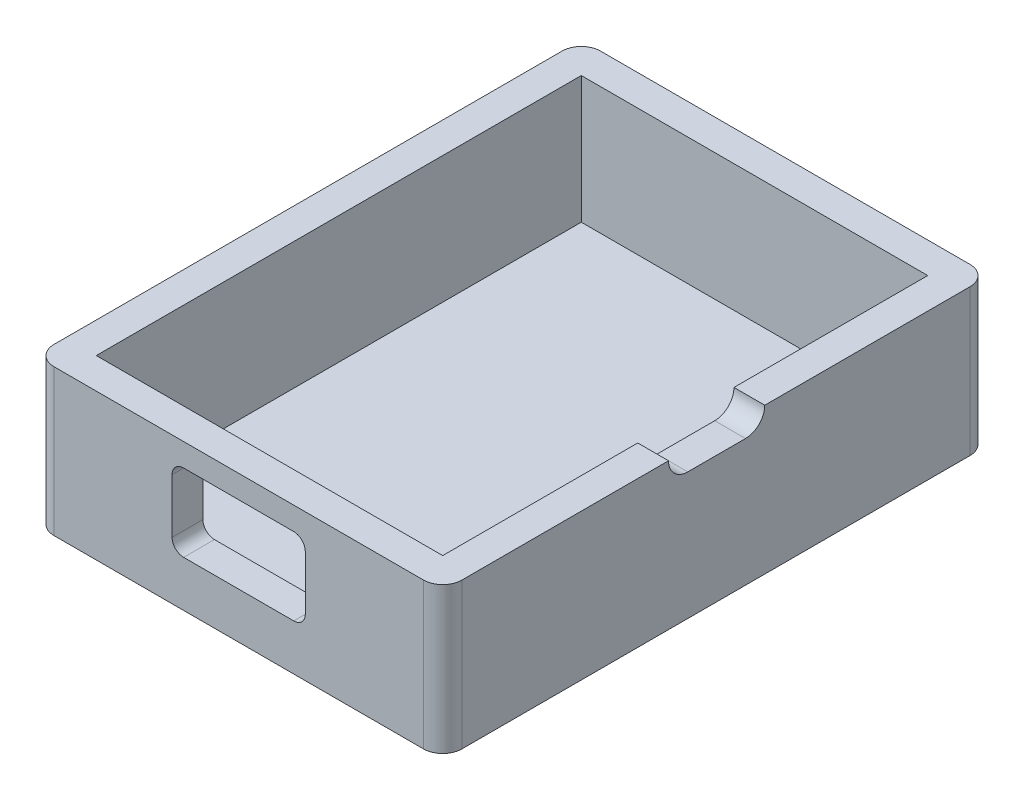
SolidWorks part; units mm, degrees
ref_plane "Front Plane" through (0, 0, 0) normal (0, 0, 1) x (1, 0, 0)
ref_plane "Top Plane" through (0, 0, 0) normal (0, 1, 0) x (1, 0, 0)
ref_plane "Right Plane" through (0, 0, 0) normal (1, 0, 0) x (0, 0, -1)
sketch "Sketch1" plane through (0, 0, 0) normal (0, 1, 0) x (1, 0, 0)
  line L1 (-53, -71) -> (53, -71)
  line L2 (-53, -71) -> (-53, 71)
  line L3 (-53, 71) -> (53, 71)
  line L4 (53, -71) -> (53, 71)
  line L5 (-53, -71) -> (53, 71) construction
  line L6 (-53, 71) -> (53, -71) construction
  point P0 (0, 0)
  dimension "D1" = 106
  dimension "D2" = 142
extrude "Boss-Extrude1" add sketch "Sketch1" along normal blind 5
sketch "Sketch2" plane through (0, 5, 0) normal (0, 1, 0) x (1, 0, 0)
  line L0 (53, -71) -> (53, 71) construction
  line L1 (-53, -71) -> (53, -71)
  line L2 (-53, -71) -> (-53, -63)
  line L3 (-53, -63) -> (53, -63)
  line L4 (53, -71) -> (53, -63)
  dimension "D1" = 8
extrude "Boss-Extrude2" add sketch "Sketch2" along normal blind 33
sketch "Sketch3" plane through (0, 5, 0) normal (0, 1, 0) x (1, 0, 0)
  line L0 (53, -63) -> (53, 71) construction
  line L1 (-53, 71) -> (53, 71)
  line L2 (-53, 71) -> (-53, 63)
  line L3 (-53, 63) -> (53, 63)
  line L4 (53, 71) -> (53, 63)
  dimension "D1" = 8
extrude "Boss-Extrude3" add sketch "Sketch3" along normal blind 33
sketch "Sketch4" plane through (0, 5, 0) normal (0, 1, 0) x (1, 0, 0)
  line L0 (53, -63) -> (-53, -63) construction
  line L1 (-53, 63) -> (-45, 63)
  line L2 (-53, 63) -> (-53, -63)
  line L3 (-53, -63) -> (-45, -63)
  line L4 (-45, 63) -> (-45, -63)
  line L6 (53, 63) -> (45, 63)
  line L7 (53, 63) -> (53, -63)
  line L8 (53, -63) -> (45, -63)
  line L9 (45, 63) -> (45, -63)
  dimension "D1" = 8
  dimension "D2" = 8
extrude "Boss-Extrude4" add sketch "Sketch4" along normal blind 33
sketch "Sketch5" plane through (0, 5, 0) normal (0, 1, 0) x (1, 0, 0)
  line L0 (45, 63) -> (45, -63) construction
  line L1 (-45, -63) -> (45, -63)
  line L2 (-45, -63) -> (-45, -48)
  line L3 (-45, -48) -> (45, -48)
  line L4 (45, -63) -> (45, -48)
  dimension "D1" = 15
extrude "Boss-Extrude5" add sketch "Sketch5" along normal blind 5
sketch "Sketch6" plane through (0, 0, 71) normal (0, 0, 1) x (1, 0, 0)
  line L0 (0, 38) -> (0, 0) construction
  line L1 (-53, 38) -> (53, 38) construction
  line L2 (-53, 22) -> (53, 22) construction
  line L3 (-53, 38) -> (-53, 0) construction
  line L4 (53, 38) -> (53, 0) construction
  line L5 (-53, 0) -> (53, 0) construction
  line L7 (-17.3, 11.95) -> (17.3, 11.95)
  line L8 (-17.3, 11.95) -> (-17.3, 32.05)
  line L9 (-17.3, 32.05) -> (17.3, 32.05)
  line L10 (17.3, 11.95) -> (17.3, 32.05)
  line L11 (-17.3, 11.95) -> (17.3, 32.05) construction
  line L12 (-17.3, 32.05) -> (17.3, 11.95) construction
  point P13 (0, 22)
  dimension "D1" = 22
  dimension "D2" = 20.1
  dimension "D3" = 34.6
extrude "Cut-Extrude1" cut sketch "Sketch6" against normal blind 10
fillet "Fillet1" radius 3 4 edges at (17.3, 32.05, 67) (17.3, 11.95, 67) (-17.3, 11.95, 67) (-17.3, 32.05, 67)
fillet "Fillet2" radius 5 4 edges at (-53, 19, 71) (53, 19, 71) (53, 19, -71) (-53, 19, -71)
sketch "Sketch8" plane through (53, 0, 0) normal (1, 0, 0) x (0, 0, -1)
  line L0 (-66, 38) -> (66, 38) construction
  line L1 (-12.3368, 33) -> (12.6632, 33)
  line L2 (-12.3368, 33) -> (-12.3368, 38)
  line L3 (-12.3368, 38) -> (12.6632, 38)
  line L4 (12.6632, 33) -> (12.6632, 38)
  line L5 (-12.3368, 33) -> (12.6632, 38) construction
  line L6 (-12.3368, 38) -> (12.6632, 33) construction
  point P0 (0.1632, 35.5)
  dimension "D1" = 25
  dimension "D2" = 5
extrude "Cut-Extrude2" cut sketch "Sketch8" against normal blind 10
fillet "Fillet3" radius 5 2 edges at (49, 33, 12.3368) (49, 33, -12.6632)
